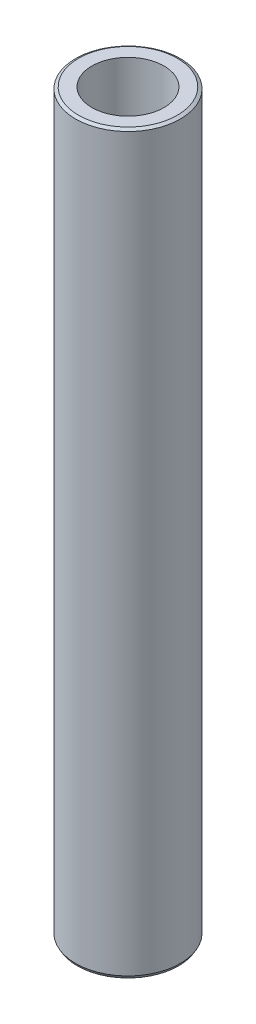
SolidWorks part; units mm, degrees
ref_plane "Front Plane" through (0, 0, 0) normal (0, 0, 1) x (1, 0, 0)
ref_plane "Top Plane" through (0, 0, 0) normal (0, 1, 0) x (1, 0, 0)
ref_plane "Right Plane" through (0, 0, 0) normal (1, 0, 0) x (0, 0, -1)
sketch "Sketch1" plane through (0, 0, 0) normal (0, 1, 0) x (1, 0, 0)
  circle A0 centre (0, 0) radius 32.5
  dimension "SHAFT_OD" = 65
extrude "Boss-Extrude1" add sketch "Sketch1" along normal blind 456.6016
sketch "Sketch2" plane through (0, 0, 0) normal (0, 1, 0) x (1, 0, 0)
  circle A0 centre (0, 0) radius 22.3705
  dimension "BORE_D" = 44.741
extrude "Cut-Extrude1" cut sketch "Sketch2" along normal through all
chamfer "Chamfer1" distance 1.078 angle 60 2 edges at (0, 456.6016, 32.5) (0, 0, 32.5) first distance on face at (0, 456.6016, 32.5) first distance on face at (0, 0, 22.3705)
